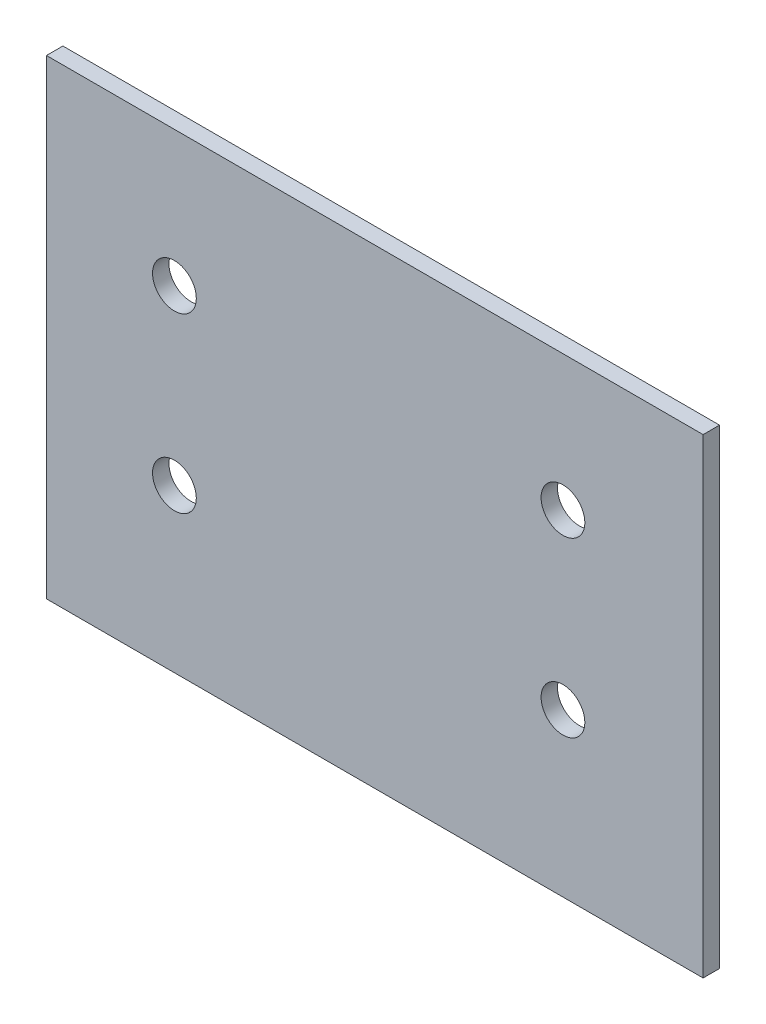
SolidWorks part; units mm, degrees
ref_plane "Front Plane" through (0, 0, 0) normal (0, 0, 1) x (1, 0, 0)
ref_plane "Top Plane" through (0, 0, 0) normal (0, 1, 0) x (1, 0, 0)
ref_plane "Right Plane" through (0, 0, 0) normal (1, 0, 0) x (0, 0, -1)
sketch "Sketch1" plane through (0, 0, 0) normal (0, 0, 1) x (1, 0, 0)
  line L1 (-38.1, 27.305) -> (38.1, 27.305)
  line L2 (-38.1, 27.305) -> (-38.1, -27.305)
  line L3 (-38.1, -27.305) -> (38.1, -27.305)
  line L4 (38.1, 27.305) -> (38.1, -27.305)
  line L5 (-38.1, 27.305) -> (38.1, -27.305) construction
  line L6 (-38.1, -27.305) -> (38.1, 27.305) construction
  point P0 (0, 0)
  dimension "D13" = 76.2
  dimension "D2" = 54.61
extrude "Boss-Extrude1" add sketch "Sketch1" along normal blind 1.905
sketch "Sketch2" plane through (0, 0, 1.905) normal (0, 0, 1) x (1, 0, 0)
  circle A0 centre (-23.2525, 11.584) radius 2.54
  circle A1 centre (-23.2525, -8.482) radius 2.54
  circle A2 centre (21.8341, 11.584) radius 2.54
  circle A3 centre (21.8341, -8.482) radius 2.54
  point P4 (-23.2951, -11.8911)
  point P5 (-24.4314, -8.6443)
  point P6 (0, 0)
  point P11 (21.6717, -8.6443)
  point P12 (21.8341, 10.0242)
  point P13 (0, 0)
  point P14 (0, 0)
  point P15 (21.8341, -8.482)
  dimension "D1" = 5.08
  dimension "D2" = 20.066
extrude "Cut-Extrude1" cut sketch "Sketch2" against normal through all
